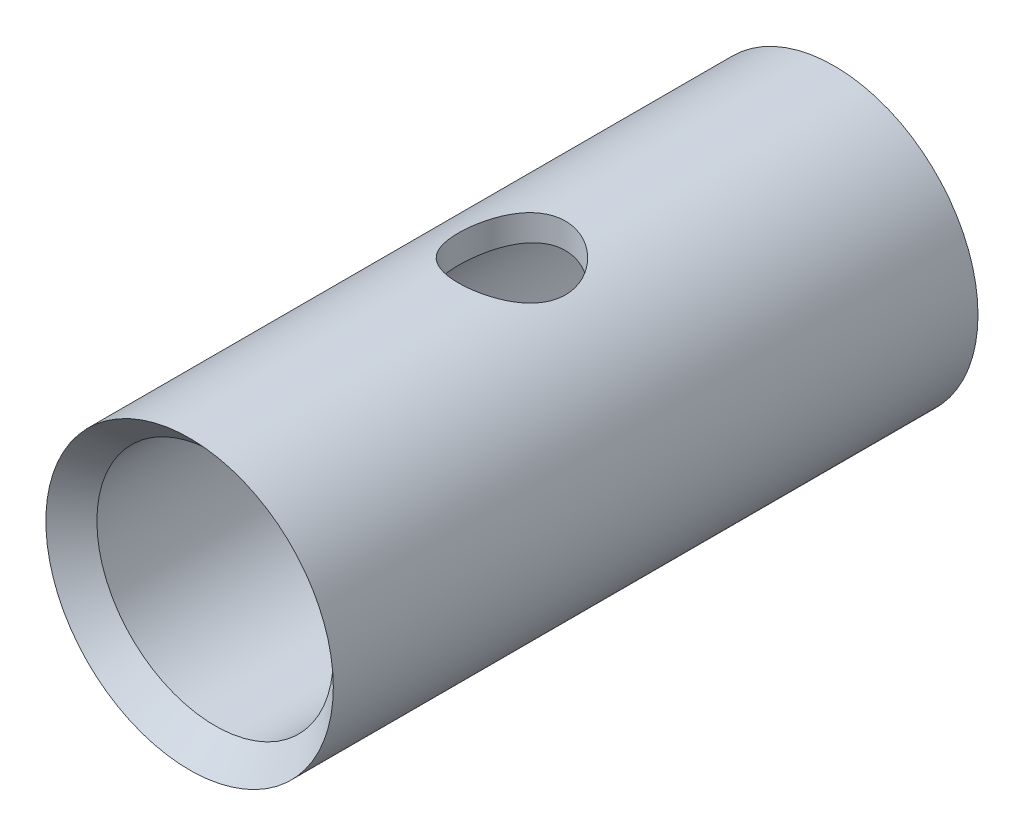
SolidWorks part; units mm, degrees
ref_plane "Alzado" through (0, 0, 0) normal (0, 0, 1) x (1, 0, 0)
ref_plane "Planta" through (0, 0, 0) normal (0, 1, 0) x (1, 0, 0)
ref_plane "Vista lateral" through (0, 0, 0) normal (1, 0, 0) x (0, 0, -1)
sketch "Croquis1" plane through (0, 0, 0) normal (0, 0, 1) x (1, 0, 0)
  circle A0 centre (0, 0) radius 13.9
  circle A1 centre (0, 0) radius 16.9
  dimension "D1" = 27.8
  dimension "D2" = 33.8
extrude "Saliente-Extruir1" add sketch "Croquis1" along normal mid plane 75.8
ref_plane "Plano1" through (0, 16.9, 0) normal (0, 1, 0) x (1, 0, 0)
sketch "Croquis2" plane through (0, 16.9, 0) normal (0, 1, 0) x (1, 0, 0)
  circle A0 centre (0, 0) radius 6.3
  dimension "D1" = 12.6
extrude "Cortar-Extruir1" cut sketch "Croquis2" against normal blind 20.8
chamfer "Chaflán1" distance 3 angle 45 2 edges at (13.9, 0, -37.9) (13.9, 0, 37.9)
